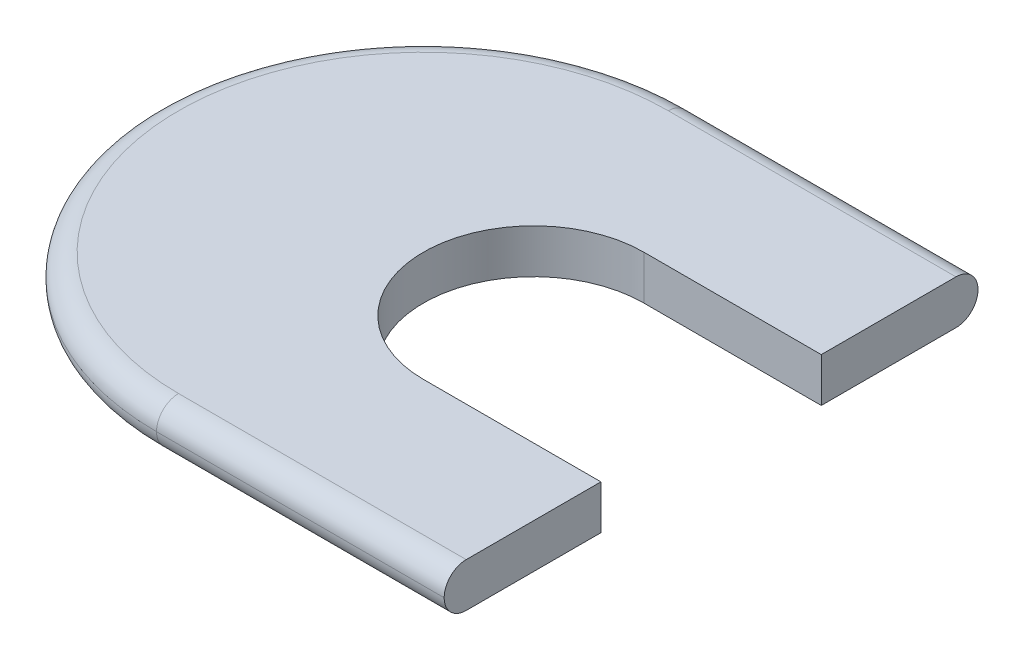
SolidWorks part; units mm, degrees
ref_plane "Front" through (0, 0, 0) normal (0, 0, 1) x (1, 0, 0)
ref_plane "Top" through (0, 0, 0) normal (0, 1, 0) x (1, 0, 0)
ref_plane "Right" through (0, 0, 0) normal (1, 0, 0) x (0, 0, -1)
sketch "Sketch1" plane through (0, 0, 0) normal (0, 1, 0) x (1, 0, 0)
  line L0 (0, 2.5) -> (4.0265, 2.5)
  line L1 (4.0265, 2.5) -> (4.0265, 6.0557)
  line L2 (4.0265, 6.0557) -> (-2.5, 6.0557)
  line L3 (-4.431, 0) -> (4.4172, 0) construction
  line L4 (0, -2.5) -> (4.0265, -2.5)
  line L5 (4.0265, -2.5) -> (4.0265, -6.0557)
  line L6 (4.0265, -6.0557) -> (-2.5, -6.0557)
  circle A0 centre (0, 0) radius 2.5 construction
  arc A1 (0, 2.5) -> (0, -2.5) centre (0, 0) ccw
  arc A2 (-2.5, 6.0557) -> (-2.5, -6.0557) centre (-2.5, 0) ccw
extrude "Boss-Extrude1" add sketch "Sketch1" along normal blind 1
fillet "Fillet1" radius 0.5 6 edges at (0.7632, 0, -6.0557) (0.7632, 0, 6.0557) (0.7632, 1, -6.0557) (0.7632, 1, 6.0557) (-8.5557, 0, 0) (-8.5557, 1, 0)
